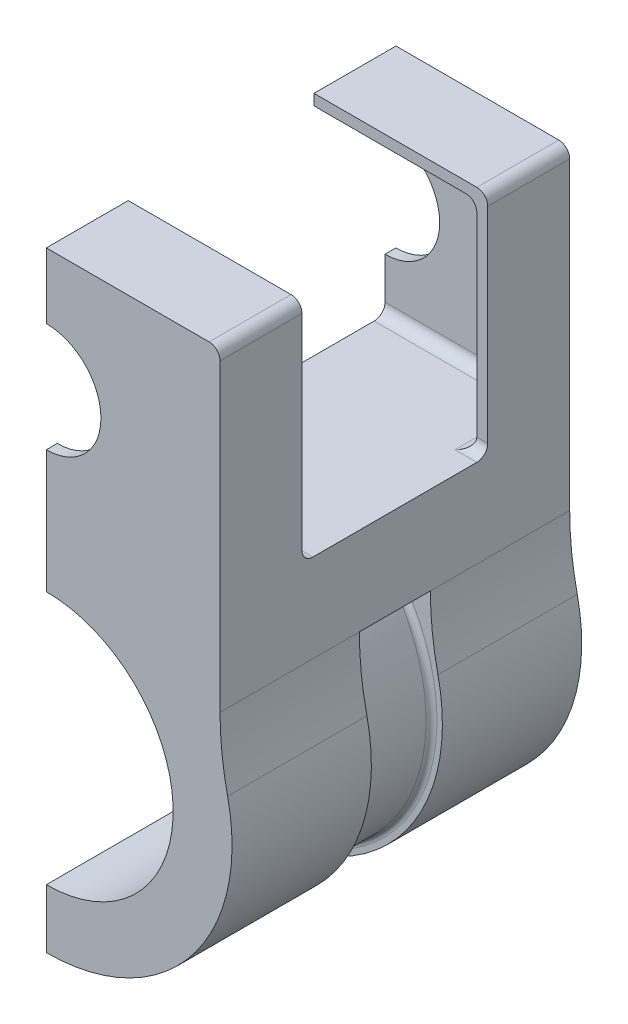
SolidWorks part; units mm, degrees
material "ABS"
ref_plane "Front Plane" through (0, 0, 0) normal (0, 0, 1) x (1, 0, 0)
ref_plane "Top Plane" through (0, 0, 0) normal (0, 1, 0) x (1, 0, 0)
ref_plane "Right Plane" through (0, 0, 0) normal (1, 0, 0) x (0, 0, -1)
sketch "Sketch1" plane through (0, 0, 0) normal (0, 0, 1) x (1, 0, 0)
  line L0 (0, 0) -> (0, 52.9844) construction
  line L1 (0, 0) -> (0, -43.18) construction
  line L2 (0, 52.9844) -> (0, 58.0644)
  line L3 (0, 83.4644) -> (0, 98.7044)
  line L4 (0, 98.7044) -> (40.386, 98.7044)
  line L5 (40.386, 98.7044) -> (40.386, 25.3987)
  line L7 (0, 52.9844) -> (0, 29.4894)
  line L8 (0, -29.4894) -> (0, -43.18)
  arc A0 (0, -29.4894) -> (0, 29.4894) centre (0, 0) ccw
  arc A1 (0, -43.18) -> (42.1474, 9.3865) centre (0, 0) ccw
  arc A2 (0, 58.0644) -> (0, 83.4644) centre (0, 70.7644) ccw
  arc A3 (42.1474, 9.3865) -> (40.386, 25.3987) centre (114.046, 25.3987) cw
  dimension "D1" = 58.9788
  dimension "D2" = 86.36
  dimension "D3" = 12.7
  dimension "D8" = 73.66
  dimension "D4" = 5.08
  dimension "D5" = 15.24
  dimension "D6" = 40.386
  dimension "D7" = 23.495
extrude "Boss-Extrude1" add sketch "Sketch1" against normal blind 81.28 contours A2 L3 L4 L5 A3 A1 L8 A0 L7 L2
sketch "Sketch3" plane through (0, 0, 0) normal (-1, 0, 0) x (0, 0, 1)
  line L0 (-78.74, 96.1644) -> (-78.74, 45.8724)
  line L1 (-78.74, 45.8724) -> (-2.54, 45.8724)
  line L2 (-2.54, 45.8724) -> (-2.54, 96.1644)
  line L3 (-2.54, 96.1644) -> (-78.74, 96.1644)
  line L4 (-81.28, 98.7044) -> (0, 98.7044) construction
  line L5 (-81.28, 83.4644) -> (-81.28, 98.7044) construction
  line L6 (0, 83.4644) -> (0, 98.7044) construction
  dimension "D1" = 2.54
  dimension "D2" = 2.54
  dimension "D3" = 2.54
  dimension "D4" = 50.292
extrude "Cut-Extrude1" cut sketch "Sketch3" against normal offset from surface (37.846 mm away) 2.54 up to face at (40.386, 62.0516, -40.64)
sketch "Sketch4" plane through (0, 98.7044, 0) normal (0, 1, 0) x (1, 0, 0)
  line L0 (0, 62.23) -> (40.386, 62.23)
  line L2 (0, 81.28) -> (0, 0) construction
  line L3 (40.386, 81.28) -> (40.386, 0) construction
  line L4 (40.386, 62.23) -> (40.386, 19.05)
  line L5 (40.386, 81.28) -> (40.386, 0) construction
  line L6 (40.386, 19.05) -> (0, 19.05)
  line L7 (0, 19.05) -> (0, 62.23)
  line L8 (0, 81.28) -> (40.386, 81.28) construction
  line L9 (0, 0) -> (40.386, 0) construction
  dimension "D1" = 19.05
  dimension "D2" = 19.05
extrude "Cut-Extrude2" cut sketch "Sketch4" against normal up to surface (52.832 mm away) up to face at (18.923, 45.8724, -40.64)
fillet "Fillet1" radius 2.54 4 edges at (18.923, 45.8724, -78.74) (37.846, 45.8724, -70.485) (18.923, 45.8724, -2.54) (37.846, 45.8724, -10.795)
fillet "Fillet2" radius 2.54 2 edges at (37.846, 96.1644, -70.485) (37.846, 96.1644, -10.795)
fillet "Fillet3" radius 2.54 2 edges at (37.846, 45.8724, -19.05) (37.846, 45.8724, -62.23)
fillet "Fillet4" radius 2.54 2 edges at (40.386, 98.7044, -9.525) (40.386, 98.7044, -71.755)
ref_axis "Axis1" through (0, 0, -81.28) along (0, 0, 1)
ref_plane "Plane1" through (0, -43.18, -81.28) normal (0, 0, 1) x (1, 0, 0)
sketch "Sketch7" plane through (0, 0, 0) normal (-1, 0, 0) x (0, 0, 1)
  line L0 (-81.28, -43.18) -> (0, -43.18) construction
  line L1 (-48.895, -43.18) -> (-32.385, -43.18)
  line L2 (-48.895, -43.18) -> (-48.895, -40.64)
  line L3 (-48.895, -40.64) -> (-32.385, -40.64)
  line L4 (-32.385, -43.18) -> (-32.385, -40.64)
  point P6 (-40.64, -40.64)
  point P7 (-40.64, -43.18)
  dimension "D1" = 16.51
  dimension "D2" = 2.54
revolve "Cut-Revolve2" cut sketch "Sketch7" angle 360 about axis through (0, 0, -81.28) along (0, 0, 1)
ref_plane "Plane2" through (42.1474, 9.3865, 0) normal (0.9761, 0.2174, 0) x (0, 0, -1)
sketch "Sketch8" plane through (42.1474, 9.3865, 0) normal (0.9761, 0.2174, 0) x (0, 0, -1)
  line L0 (81.28, 0) -> (0, 0) construction
  line L1 (32.385, 0) -> (48.895, 0)
  line L2 (32.385, 0) -> (32.385, 16.0122)
  line L3 (32.385, 16.0122) -> (48.895, 16.0122)
  line L4 (48.895, 0) -> (48.895, 16.0122)
  line L5 (81.28, 16.0122) -> (0, 16.0122) construction
  point P8 (40.64, 16.0122)
  point P9 (40.64, 16.0122)
  dimension "D1" = 16.51
extrude "Cut-Extrude4" cut sketch "Sketch8" against normal up to surface and the other way blind 2.54 contours L4 L3 L2 L1 up to face at (20.32, 0, -40.64)
fillet "Fillet5" radius 1.27 2 edges at (40.64, 0, -48.895) (40.64, 0, -32.385)
